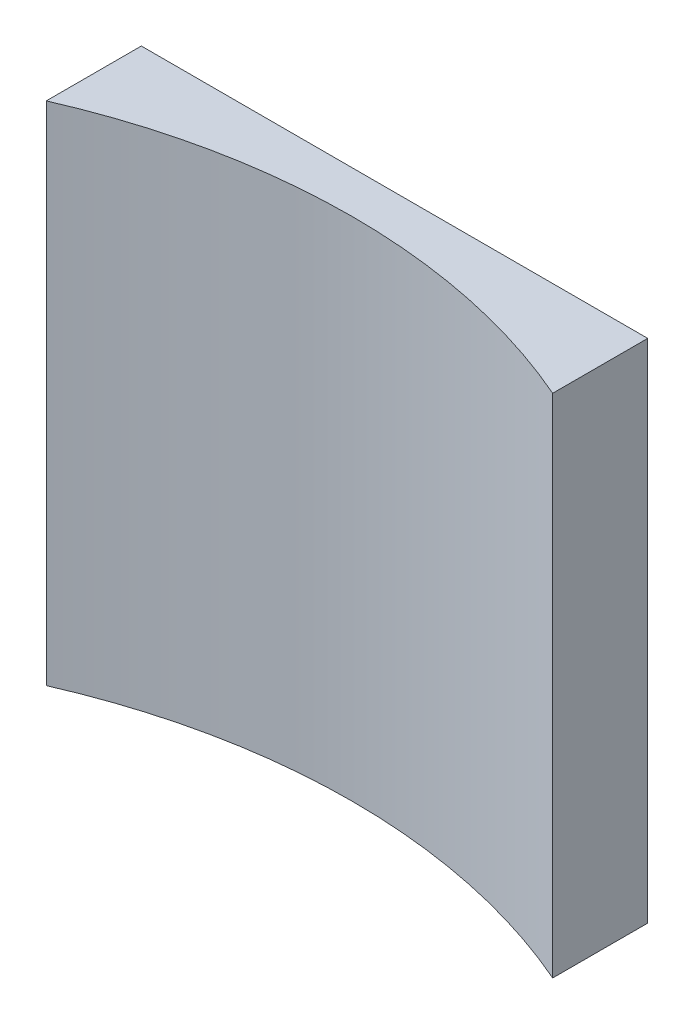
SolidWorks part; units mm, degrees
ref_plane "Plano frontal" through (0, 0, 0) normal (0, 0, 1) x (1, 0, 0)
ref_plane "Plano superior" through (0, 0, 0) normal (0, 1, 0) x (1, 0, 0)
ref_plane "Plano direito" through (0, 0, 0) normal (1, 0, 0) x (0, 0, -1)
sketch "Esboço2" plane through (0, 0, 0) normal (0, 1, 0) x (1, 0, 0)
  line L0 (-60, 0) -> (60, 0)
  line L1 (-60, -22.5227) -> (-60, 0)
  line L2 (60, 0) -> (60, -22.5227)
  arc A0 (-60, -22.5227) -> (60, -22.5227) centre (0, -160) cw
  point P4 (0, 0)
  point P8 (0, -10)
  dimension "D2" = 150
  dimension "D1" = 120
  dimension "D3" = 10
extrude "Ressalto-extrusão1" add sketch "Esboço2" along normal mid plane 120
shell "Casca1" thickness 3.5 removed face at (0, 0, 0)
ref_plane "Plano1" through (0, 0, 0) normal (0, 0, -1) x (-1, 0, 0)
sketch "Esboço7" plane through (0, 0, 0) normal (0, 0, -1) x (-1, 0, 0)
  line L5 (-56.5, -56.5) -> (56.5, -56.5)
  line L6 (-56.5, -56.5) -> (-56.5, 56.5)
  line L11 (-56.5, 56.5) -> (56.5, 56.5)
  line L12 (56.5, -56.5) -> (56.5, 56.5)
  line L13 (-56.5, -56.5) -> (56.5, 56.5) construction
  line L14 (-56.5, 56.5) -> (56.5, -56.5) construction
  line L15 (-52, -52) -> (52, -52)
  line L16 (-52, -52) -> (-52, 52)
  line L17 (-52, 52) -> (52, 52)
  line L18 (52, -52) -> (52, 52)
  line L19 (-52, -52) -> (52, 52) construction
  line L20 (-52, 52) -> (52, -52) construction
  point P0 (0, 0)
  point P5 (0, 0)
  dimension "D1" = 113
  dimension "D2" = 104
  dimension "D3" = 104
extrude "Ressalto-extrusão3" add sketch "Esboço7" along normal mid plane 6 separate body
chamfer "Chanfro1" distance 1 angle 45 4 edges at (56.5, 0, -3) (0, -56.5, -3) (-56.5, 0, -3) (0, 56.5, -3)
sketch "Esboço3" plane through (0, 0, 0) normal (0, 0, -1) x (-1, 0, 0)
  line L0 (-46.5, 51.5) -> (-46.5, 56.5)
  line L1 (-56.5, 56.5) -> (56.5, 56.5) construction
  line L2 (-56.5, 56.5) -> (-56.5, -56.5) construction
  line L3 (-56.5, 56.5) -> (56.5, 56.5) construction
  line L4 (-46.5, 56.5) -> (-56.5, 56.5)
  line L5 (-51.5, 46.5) -> (-56.5, 46.5)
  line L6 (-56.5, 56.5) -> (-56.5, -56.5) construction
  line L7 (-56.5, 46.5) -> (-56.5, 56.5)
  line L8 (0, 12.3875) -> (0, -12.3875) construction
  line L9 (56.5, 46.5) -> (56.5, 56.5)
  line L10 (51.5, 46.5) -> (56.5, 46.5)
  line L11 (46.5, 56.5) -> (56.5, 56.5)
  line L12 (46.5, 51.5) -> (46.5, 56.5)
  line L13 (12.3875, 0) -> (-12.3875, 0) construction
  line L14 (46.5, -51.5) -> (46.5, -56.5)
  line L15 (46.5, -56.5) -> (56.5, -56.5)
  line L16 (51.5, -46.5) -> (56.5, -46.5)
  line L17 (56.5, -46.5) -> (56.5, -56.5)
  line L18 (-56.5, -46.5) -> (-56.5, -56.5)
  line L19 (-51.5, -46.5) -> (-56.5, -46.5)
  line L20 (-46.5, -56.5) -> (-56.5, -56.5)
  line L21 (-46.5, -51.5) -> (-46.5, -56.5)
  line L22 (-51.5, 5) -> (-56.5, 5)
  line L23 (-56.5, 5) -> (-56.5, -5)
  line L24 (-56.5, -5) -> (-51.5, -5)
  line L25 (56.5, -5) -> (51.5, -5)
  line L26 (56.5, 5) -> (56.5, -5)
  line L27 (51.5, 5) -> (56.5, 5)
  line L28 (-5, 51.5) -> (-5, 56.5)
  line L29 (5, 51.5) -> (5, 56.5)
  line L30 (5, 56.5) -> (-5, 56.5)
  line L31 (5, -56.5) -> (-5, -56.5)
  line L32 (5, -51.5) -> (5, -56.5)
  line L33 (-5, -51.5) -> (-5, -56.5)
  arc A0 (-51.5, 46.5) -> (-46.5, 51.5) centre (-51.5, 51.5) ccw
  arc A1 (51.5, 46.5) -> (46.5, 51.5) centre (51.5, 51.5) cw
  arc A2 (51.5, -46.5) -> (46.5, -51.5) centre (51.5, -51.5) ccw
  arc A3 (-51.5, -46.5) -> (-46.5, -51.5) centre (-51.5, -51.5) cw
  arc A4 (-51.5, -5) -> (-51.5, 5) centre (-51.5, 0) ccw
  arc A5 (51.5, -5) -> (51.5, 5) centre (51.5, 0) cw
  arc A6 (-5, 51.5) -> (5, 51.5) centre (0, 51.5) ccw
  arc A7 (-5, -51.5) -> (5, -51.5) centre (0, -51.5) cw
  dimension "D1" = 10
  dimension "D2" = 10
  dimension "D3" = 10
extrude "Ressalto-extrusão2" add sketch "Esboço3" against normal through all
sketch "Esboço4" plane through (0, 0, 0) normal (0, 1, 0) x (1, 0, 0)
  line L0 (-60, -22.5227) -> (-60, -33.5643)
  line L1 (-60, -33.5643) -> (60, -33.5643)
  line L2 (60, -33.5643) -> (60, -22.5227)
  arc A0 (-60, -22.5227) -> (60, -22.5227) centre (0, -160) cw
extrude "Corte-extrusão1" cut sketch "Esboço4" against normal through all both and the other way through all
sketch "Esboço8" plane through (0, 0, 0) normal (0, 0, 1) x (1, 0, 0)
  line L0 (-46.5, 51.5) -> (-46.5, 56.5)
  line L4 (-46.5, 56.5) -> (-56.5, 56.5)
  line L5 (-51.5, 46.5) -> (-56.5, 46.5)
  line L7 (-56.5, 46.5) -> (-56.5, 56.5)
  line L9 (56.5, 46.5) -> (56.5, 56.5)
  line L10 (51.5, 46.5) -> (56.5, 46.5)
  line L11 (46.5, 56.5) -> (56.5, 56.5)
  line L12 (46.5, 51.5) -> (46.5, 56.5)
  line L14 (46.5, -51.5) -> (46.5, -56.5)
  line L15 (46.5, -56.5) -> (56.5, -56.5)
  line L16 (51.5, -46.5) -> (56.5, -46.5)
  line L17 (56.5, -46.5) -> (56.5, -56.5)
  line L18 (-56.5, -46.5) -> (-56.5, -56.5)
  line L19 (-51.5, -46.5) -> (-56.5, -46.5)
  line L20 (-46.5, -56.5) -> (-56.5, -56.5)
  line L21 (-46.5, -51.5) -> (-46.5, -56.5)
  line L22 (-51.5, 5) -> (-56.5, 5)
  line L23 (-56.5, 5) -> (-56.5, -5)
  line L24 (-56.5, -5) -> (-51.5, -5)
  line L25 (56.5, -5) -> (51.5, -5)
  line L26 (56.5, 5) -> (56.5, -5)
  line L27 (51.5, 5) -> (56.5, 5)
  line L28 (-5, 51.5) -> (-5, 56.5)
  line L29 (5, 51.5) -> (5, 56.5)
  line L30 (5, 56.5) -> (-5, 56.5)
  line L31 (5, -56.5) -> (-5, -56.5)
  line L32 (5, -51.5) -> (5, -56.5)
  line L33 (-5, -51.5) -> (-5, -56.5)
  arc A0 (-51.5, 46.5) -> (-46.5, 51.5) centre (-51.5, 51.5) ccw
  arc A1 (51.5, 46.5) -> (46.5, 51.5) centre (51.5, 51.5) cw
  arc A2 (51.5, -46.5) -> (46.5, -51.5) centre (51.5, -51.5) ccw
  arc A3 (-51.5, -46.5) -> (-46.5, -51.5) centre (-51.5, -51.5) cw
  arc A4 (-51.5, -5) -> (-51.5, 5) centre (-51.5, 0) ccw
  arc A5 (51.5, -5) -> (51.5, 5) centre (51.5, 0) cw
  arc A6 (-5, 51.5) -> (5, 51.5) centre (0, 51.5) ccw
  arc A7 (-5, -51.5) -> (5, -51.5) centre (0, -51.5) cw
  dimension "D1" = 10
  dimension "D2" = 10
  dimension "D3" = 10
extrude "Corte-extrusão2" cut sketch "Esboço8" against normal blind 3
